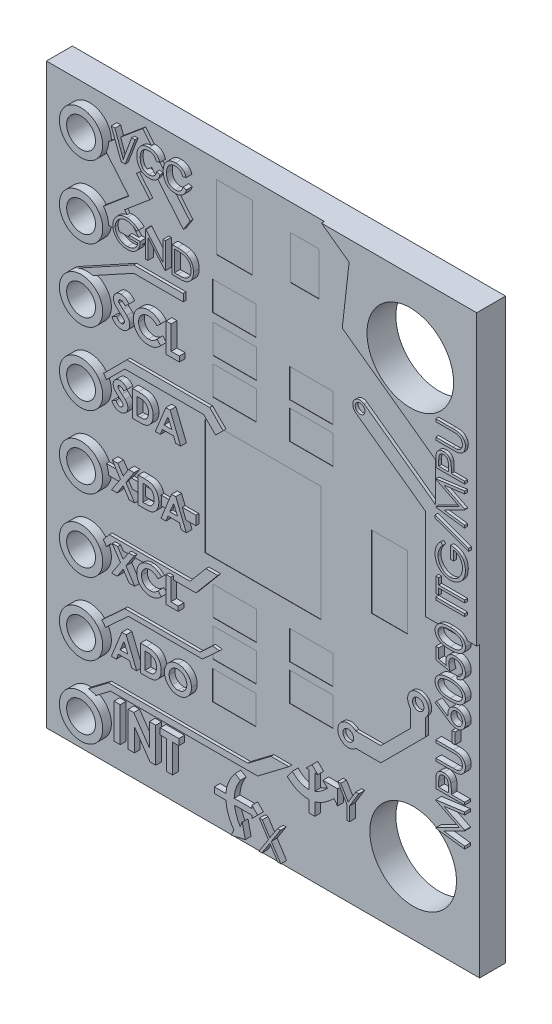
SolidWorks part; units mm, degrees
ref_plane "Plan de face" through (0, 0, 0) normal (0, 0, 1) x (1, 0, 0)
ref_plane "Plan de dessus" through (0, 0, 0) normal (0, 1, 0) x (1, 0, 0)
ref_plane "Plan de droite" through (0, 0, 0) normal (1, 0, 0) x (0, 0, -1)
sketch "Esquisse1" plane through (0, 0, 0) normal (0, 0, 1) x (1, 0, 0)
  line L0 (0, 0) -> (0, 9.701) construction
  line L1 (7.5, -10) -> (-7.5, -10)
  line L2 (7.5, -10) -> (7.5, 10)
  line L3 (7.5, 10) -> (-7.5, 10)
  line L4 (-7.5, -10) -> (-7.5, 10)
  line L5 (7.5, -10) -> (-7.5, 10) construction
  line L6 (7.5, 10) -> (-7.5, -10) construction
  line L7 (-7.2449, 0) -> (8.3434, 0) construction
  circle A0 centre (5.2, 7.5) radius 1.5
  circle A1 centre (5.2, -7.5) radius 1.5
  point P0 (0, 0)
  dimension "D3" = 3
  dimension "D1" = 20
  dimension "D2" = 15
  dimension "D4" = 2.5
  dimension "D5" = 2.3
extrude "Boss.-Extru.1" add sketch "Esquisse1" along normal blind 0.9
sketch "Esquisse2" plane through (0, 0, 0.9) normal (0, 0, 1) x (1, 0, 0)
  line L0 (-7.5, 10) -> (-7.5, -10) construction
  line L1 (7.5, 10) -> (-7.5, 10) construction
  circle A0 centre (-6, 8.75) radius 0.75
  circle A1 centre (-6, 8.75) radius 0.5
  dimension "D1" = 1.5
  dimension "D2" = 0.25
  dimension "D5" = 1
  dimension "D3" = 1.5
  dimension "D4" = 1.25
extrude "Enlèv. mat.-Extru.3" cut sketch "Esquisse2" against normal through all contours A1 region at (-6, 8.75, 0.9)
extrude "Boss.-Extru.2" add sketch "Esquisse2<3>" along normal blind 0.3 contours A1 | A0
sketch "Esquisse2<3>" plane through (0, 0, 0.9) normal (0, 0, 1) x (1, 0, 0) same geometry as "Esquisse2"
pattern_linear "Répétition linéaire1" count 8 spacing 2.5 along (0, -1, 0) of "Enlèv. mat.-Extru.3", "Boss.-Extru.2"
sketch "Esquisse4" plane through (0, 0, 0.9) normal (0, 0, 1) x (1, 0, 0)
  line L0 (-5.6839, -8.0698) -> (-5.1788, -7.6865)
  line L1 (-5.1788, -7.6865) -> (-0.0869, -7.6865)
  line L2 (-5.3559, -5.8657) -> (-4.5626, -5.1342)
  line L3 (-5.9485, -8.0018) -> (-5.25, -7.4716)
  line L4 (-5.25, -7.4716) -> (-0.425, -7.4716)
  line L5 (-0.425, -7.4716) -> (0.3769, -6.863)
  line L6 (-0.0869, -7.6865) -> (0.9981, -6.863)
  line L7 (-4.5626, -5.1342) -> (-1.9962, -5.1342)
  line L8 (-1.9962, -5.1342) -> (-1.4096, -4.5933)
  line L9 (-1.6459, -4.5662) -> (-2.0788, -4.9655)
  line L10 (-2.0788, -4.9655) -> (-4.6846, -4.9655)
  line L11 (-4.6846, -4.9655) -> (-5.4857, -5.7041)
  line L12 (-5.3211, -3.4313) -> (-5.1788, -3.2623)
  line L13 (-5.1788, -3.2623) -> (-2.2245, -3.2623)
  line L14 (-2.2245, -3.2623) -> (-1.4657, -2.3614)
  line L15 (-1.4657, -2.3614) -> (-1.876, -2.3614)
  line L16 (-1.876, -2.3614) -> (-2.4268, -3.0153)
  line L17 (-2.4268, -3.0153) -> (-5.2223, -3.0153)
  line L18 (-5.2223, -3.0153) -> (-5.4303, -3.2623)
  line L19 (-5.25, -1.25) -> (-2.2245, -1.25)
  line L20 (-5.3211, -0.9313) -> (-2.2245, -0.9313)
  line L21 (-5.326, 1.579) -> (-4.6846, 2.2204)
  line L22 (-4.6846, 2.2204) -> (-1.952, 2.2204)
  line L23 (-1.952, 2.2204) -> (-1.5418, 1.8102)
  line L24 (-1.5418, 1.8102) -> (-1.2801, 2.0719)
  line L25 (-1.2801, 2.0719) -> (-1.744, 2.5358)
  line L26 (-1.744, 2.5358) -> (-4.6086, 2.5358)
  line L27 (-4.6086, 2.5358) -> (-5.4195, 1.7249)
  line L28 (-2.2245, -0.9313) -> (-2.2245, -1.25)
  line L29 (0.3769, -6.863) -> (0.9981, -6.863)
  line L30 (-5.7904, 4.4701) -> (-4.3767, 5.2455)
  line L31 (-4.3767, 5.2455) -> (-2.6617, 5.2455)
  line L32 (-2.6617, 5.2455) -> (-2.6617, 5.4958)
  line L33 (-2.6617, 5.4958) -> (-4.3767, 5.4958)
  line L34 (-4.3767, 5.4958) -> (-6.3607, 4.4076)
  line L35 (-5.25, 6.25) -> (-4.0664, 6.25)
  line L36 (-4.0664, 6.25) -> (-4.6907, 6.9959)
  line L37 (-4.6907, 6.9959) -> (-3.8171, 7.7316)
  line L38 (-3.8171, 7.7316) -> (-4.2836, 8.289)
  line L39 (-4.2836, 8.289) -> (-3.7546, 8.7317)
  line L40 (-3.7546, 8.7317) -> (-2.6559, 7.4189)
  line L41 (-4.0664, 9.7406) -> (-5.25, 8.75)
  line L42 (-5.3315, 8.41) -> (-4.5476, 7.4734)
  line L43 (-4.5476, 7.4734) -> (-5.4264, 6.7332)
  line L44 (-4.0664, 9.7406) -> (-2.4268, 7.7815)
  line L45 (-1.6459, -4.5662) -> (-1.4096, -4.5933)
  line L46 (6.0756, 4.8784) -> (2.8432, 7.2132)
  line L47 (2.8432, 7.2132) -> (3.0831, 9.3079)
  line L48 (3.0831, 9.3079) -> (2.1248, 10)
  line L49 (7.5, 10) -> (-7.5, 10) construction
  line L50 (6.0756, 4.8784) -> (6.0756, 3.5316)
  line L51 (6.0756, 3.5316) -> (3.6093, 5.3131)
  line L52 (3.3136, 4.9036) -> (5.7336, 3.1556)
  line L53 (5.7336, 3.1556) -> (5.7336, 0)
  line L54 (5.7336, 0) -> (7.5, 0)
  line L55 (7.5, -10) -> (7.5, 10) construction
  line L56 (5.7336, -3.0153) -> (5.7336, -3.6039)
  line L57 (5.7336, -3.6039) -> (4.18, -5.1574)
  line L58 (4.18, -5.1574) -> (3.3136, -5.1574)
  line L59 (3.3136, -4.639) -> (4.18, -4.639)
  line L60 (4.18, -4.639) -> (5.2151, -3.6039)
  line L61 (5.2151, -3.6039) -> (5.2151, -3.0153)
  line L62 (-2.4268, 7.7815) -> (-2.6559, 7.4189)
  circle A0 centre (-6, -8.75) radius 0.75 construction
  circle A1 centre (-6, -8.75) radius 0.75 construction
  arc A2 (-5.6839, -8.0698) -> (-5.9485, -8.0018) centre (-6, -8.75) ccw
  circle A3 centre (-6, -6.25) radius 0.75 construction
  circle A4 centre (-6, -3.75) radius 0.75 construction
  circle A5 centre (-6, -3.75) radius 0.75 construction
  circle A6 centre (-6, -1.25) radius 0.75 construction
  circle A7 centre (-6, 1.25) radius 0.75 construction
  circle A8 centre (-6, 3.75) radius 0.75 construction
  circle A9 centre (-6, 3.75) radius 0.75 construction
  arc A10 (-5.7904, 4.4701) -> (-6.3607, 4.4076) centre (-6, 3.75) ccw
  circle A11 centre (-6, 6.25) radius 0.75 construction
  circle A12 centre (-6, 8.75) radius 0.75 construction
  circle A13 centre (-6, 8.75) radius 0.75 construction
  arc A14 (-5.3315, 8.41) -> (-5.25, 8.75) centre (-6, 8.75) ccw
  circle A16 centre (-6, 6.25) radius 0.75 construction
  arc A17 (-5.25, 6.25) -> (-5.4264, 6.7332) centre (-6, 6.25) ccw
  circle A18 centre (-6, 1.25) radius 0.75 construction
  arc A19 (-5.326, 1.579) -> (-5.4195, 1.7249) centre (-6, 1.25) ccw
  circle A20 centre (-6, -1.25) radius 0.75 construction
  arc A21 (-5.25, -1.25) -> (-5.3211, -0.9313) centre (-6, -1.25) ccw
  circle A22 centre (-6, -6.25) radius 0.75 construction
  arc A23 (-5.3559, -5.8657) -> (-5.4857, -5.7041) centre (-6, -6.25) ccw
  arc A24 (-5.3211, -3.4313) -> (-5.4303, -3.2623) centre (-6, -3.75) ccw
  arc A25 (3.3136, 4.9036) -> (3.6093, 5.3131) centre (3.4615, 5.1083) cw
  arc A26 (3.6093, 5.3131) -> (3.3136, 4.9036) centre (3.4615, 5.1083) ccw
  circle A27 centre (3.4615, 5.1083) radius 0.1681
  arc A28 (5.2151, -3.0153) -> (5.7336, -3.0153) centre (5.4743, -2.7561) cw
  arc A29 (3.3136, -4.639) -> (3.3136, -5.1574) centre (3.0544, -4.8982) ccw
  circle A30 centre (3.0544, -4.8982) radius 0.1869
  circle A31 centre (5.4743, -2.7561) radius 0.1967
  circle M44 centre (-6, 8.75) radius 0.75
  circle M45 centre (5.2, 7.5) radius 1.5
  line M48 (7.5, -10) -> (7.5, 10)
  line M49 (7.5, 10) -> (-7.5, 10)
  circle M51 centre (-6, 6.25) radius 0.75
extrude "Boss.-Extru.3" add sketch "Esquisse4" along normal blind 0.1 contours A25 L52 L53 L54 L48 L47 L46 L50 L51 A27 M48 M49 M45 | L59 A29 L58 L57 L56 A28 L61 L60 A31 A30 | L62 L44 L41 L42 L43 L35 L36 L37 L38 L39 L40 M44 M51 | L5 L29 L6 L1 L0 A2 L3 L4 | L24 L25 L26 L27 A19 L21 L22 L23 | L33 L34 A10 L30 L31 L32 | L20 L28 L19 A21 | L14 L15 L16 L17 L18 A24 L12 L13 | L8 L45 L9 L10 L11 A23 L2 L7 region at (-4.2587, 8.0814, 0.9) region at (5.8792, 5.6723, 0.9) region at (5.6909, -3.3096, 0.9)
sketch "Esquisse12" plane through (0, 0, 0.9) normal (0, 0, 1) x (1, 0, 0)
  line L0 (-5.0695, 8.4732) -> (-2.0314, 8.4732) construction
  line L1 (-5.0695, 5.9732) -> (-2.0314, 5.9732) construction
  line L2 (-5.0695, 3.4732) -> (-2.0314, 3.4732) construction
  line L3 (-5.0695, 0.9732) -> (-2.0314, 0.9732) construction
  line L4 (-5.0695, -1.5268) -> (-2.0314, -1.5268) construction
  line L5 (-5.0695, -4.0268) -> (-2.0314, -4.0268) construction
  line L6 (-5.0695, -6.5268) -> (-2.0314, -6.5268) construction
  line L7 (-5.0695, -9.0268) -> (-2.0314, -9.0268) construction
  text T0 "VCC" font "@Arial Unicode MS" height 0.9
  text T1 "GND" font "Century Gothic" height 0.9
  text T2 "SCL\r\n" font "Century Gothic" height 1
  text T3 "SDA" font "Century Gothic" height 0.9
  text T4 "XDA" font "Century Gothic" height 0.9
  text T5 "XCL" font "Century Gothic" height 0.9
  text T6 "ADO" font "Century Gothic" height 0.9
  text T7 "INT" font "Century Gothic" height 1.2
  dimension "D1" = 8
extrude "Boss.-Extru.4" add sketch "Esquisse12" along normal blind 0.2
sketch "Esquisse13" plane through (0, 0, 0.9) normal (0, 0, 1) x (1, 0, 0)
  line L0 (-1.4855, -8.8592) -> (-1.085, -8.8592)
  line L1 (-0.1855, -8.8592) -> (-0.1855, -8.9592)
  line L2 (-0.1855, -8.9592) -> (0.0145, -8.7592)
  line L3 (0.0145, -8.7592) -> (-0.1855, -8.5592)
  line L4 (-0.1855, -8.5592) -> (-0.1855, -8.6592)
  line L5 (-0.1855, -8.6592) -> (-0.7975, -8.6592)
  line L6 (-1.4855, -8.6592) -> (-1.4855, -8.8592)
  line L7 (1.997, -7.8033) -> (1.997, -7.3665)
  line L8 (1.997, -6.5033) -> (2.097, -6.5033)
  line L9 (2.097, -6.5033) -> (1.897, -6.3033)
  line L10 (1.897, -6.3033) -> (1.697, -6.5033)
  line L11 (1.697, -6.5033) -> (1.797, -6.5033)
  line L12 (1.797, -6.5033) -> (1.797, -7.0998)
  line L13 (1.797, -7.8033) -> (1.997, -7.8033)
  line L14 (-0.8058, -9.6098) -> (-0.9072, -9.8186)
  line L15 (-0.9072, -9.8186) -> (-0.4139, -9.7084)
  line L16 (-0.4139, -9.7084) -> (-0.5192, -9.2372)
  line L17 (-0.5192, -9.2372) -> (-0.5935, -9.4085)
  line L18 (-0.5829, -8.0126) -> (-0.771, -7.9044)
  line L19 (2.4338, -6.7421) -> (2.2729, -6.5837)
  line L20 (2.2729, -6.5837) -> (2.783, -6.5837)
  line L21 (2.783, -6.5837) -> (2.783, -7.1)
  line L22 (2.783, -7.1) -> (2.6565, -6.9399)
  line L23 (1.2146, -6.8436) -> (1.0366, -7.0862)
  line L24 (-1.0844, -8.6592) -> (-1.4855, -8.6592)
  line L25 (1.797, -7.3995) -> (1.797, -7.8033)
  line L26 (-0.7867, -8.8592) -> (-0.1855, -8.8592)
  line L27 (1.997, -7.0528) -> (1.997, -6.5033)
  line L28 (0.0145, -9.8186) -> (1.6804, -9.8186) construction
  line L29 (2.7344, -7.3665) -> (3.9669, -7.3665) construction
  spline S0 degree 2 poles (-0.771, -7.9044) (-1.0541, -8.255) (-1.0844, -8.6592) knots 0 0 0 0.442891 0.442891 0.442891
  spline S1 degree 3 poles (-0.5829, -8.0126) (-0.7189, -8.2209) (-0.7905, -8.4364) (-0.7975, -8.6592) knots 0 0 0 0 0.480183 0.480183 0.480183 0.480183
  spline S2 degree 3 poles (1.0366, -7.0862) (1.2858, -7.3076) (1.5393, -7.412) (1.797, -7.3995) knots 0 0 0 0 0.477983 0.477983 0.477983 0.477983
  spline S3 degree 3 poles (1.2146, -6.8436) (1.4015, -7.0294) (1.5957, -7.1148) (1.797, -7.0998) knots 0 0 0 0 0.495666 0.495666 0.495666 0.495666
  spline S4 degree 3 poles (-1.085, -8.8592) (-1.0812, -8.9137) (-1.0473, -9.18) (-0.9384, -9.4353) (-0.8096, -9.608) (-0.8058, -9.6098) knots 0.552421 0.552421 0.552421 0.552421 0.642107 0.993388 1 1 1 1
  spline S5 degree 2 poles (-0.7867, -8.8592) (-0.7499, -9.1271) (-0.5935, -9.4085) knots 0.622472 0.622472 0.622472 1 1 1
  spline S6 degree 3 poles (1.997, -7.0528) (2.1392, -6.9971) (2.2848, -6.8935) (2.4338, -6.7421) knots 0.657917 0.657917 0.657917 0.657917 1 1 1 1
  spline S7 degree 2 poles (1.997, -7.3665) (2.3223, -7.2754) (2.6565, -6.9399) knots 0.601114 0.601114 0.601114 1 1 1
  text T0 "Y" font "Century Gothic" height 1
  text T1 "X" font "Century Gothic" height 1
  dimension "D1" = 0.2
  dimension "D2" = 1.3
  dimension "D3" = 0.1
  dimension "D4" = 0.1
  dimension "D5" = 0.2
  dimension "D6" = 0.2
  dimension "D7" = 1.3
  dimension "D8" = 0.1
  dimension "D9" = 0.2
  dimension "D10" = 0.1
extrude "Boss.-Extru.5" add sketch "Esquisse13" along normal blind 0.2
sketch "Esquisse14" plane through (0, 0, 0.9) normal (0, 0, 1) x (1, 0, 0)
  line L0 (7.1827, -6.2733) -> (7.1827, 6.2188) construction
  text T0 "MPU-6050 ITG/MPU" font "Century Gothic" height 1
extrude "Boss.-Extru.6" add sketch "Esquisse14" along normal blind 0.2
sketch "Esquisse15" plane through (0, 0, 0.9) normal (0, 0, 1) x (1, 0, 0)
  line L0 (-1.7334, 4.0536) -> (-0.2334, 4.0536)
  line L1 (2, -2) -> (-2, -2)
  line L2 (2, -2) -> (2, 2)
  line L3 (2, 2) -> (-2, 2)
  line L4 (-2, -2) -> (-2, 2)
  line L5 (2, -2) -> (-2, 2) construction
  line L6 (2, 2) -> (-2, -2) construction
  line L7 (-0.3655, 7.1404) -> (-1.6155, 7.1404)
  line L8 (-0.3655, 7.1404) -> (-0.3655, 9.3904)
  line L9 (-0.3655, 9.3904) -> (-1.6155, 9.3904)
  line L10 (-1.6155, 7.1404) -> (-1.6155, 9.3904)
  line L11 (-0.3655, 7.1404) -> (-1.6155, 9.3904) construction
  line L12 (-0.3655, 9.3904) -> (-1.6155, 7.1404) construction
  line L13 (5.0118, -0.9331) -> (3.7618, -0.9331)
  line L14 (5.0118, -0.9331) -> (5.0118, 1.5669)
  line L15 (5.0118, 1.5669) -> (3.7618, 1.5669)
  line L16 (3.7618, -0.9331) -> (3.7618, 1.5669)
  line L17 (5.0118, -0.9331) -> (3.7618, 1.5669) construction
  line L18 (5.0118, 1.5669) -> (3.7618, -0.9331) construction
  line L19 (1.9439, 7.5822) -> (0.9439, 7.5822)
  line L20 (1.9439, 7.5822) -> (1.9439, 9.0822)
  line L21 (1.9439, 9.0822) -> (0.9439, 9.0822)
  line L22 (0.9439, 7.5822) -> (0.9439, 9.0822)
  line L23 (1.9439, 7.5822) -> (0.9439, 9.0822) construction
  line L24 (1.9439, 9.0822) -> (0.9439, 7.5822) construction
  line L25 (-1.7405, 6.338) -> (-0.2405, 6.338)
  line L26 (-1.7405, 6.338) -> (-1.7405, 5.338)
  line L27 (-1.7405, 5.338) -> (-0.2405, 5.338)
  line L28 (-0.2405, 6.338) -> (-0.2405, 5.338)
  line L29 (-1.7405, 6.338) -> (-0.2405, 5.338) construction
  line L30 (-1.7405, 5.338) -> (-0.2405, 6.338) construction
  line L31 (0.9166, 5.0536) -> (2.4166, 5.0536)
  line L32 (0.9166, 5.0536) -> (0.9166, 4.0536)
  line L33 (0.9166, 4.0536) -> (2.4166, 4.0536)
  line L34 (2.4166, 5.0536) -> (2.4166, 4.0536)
  line L35 (0.9166, 5.0536) -> (2.4166, 4.0536) construction
  line L36 (0.9166, 4.0536) -> (2.4166, 5.0536) construction
  line L37 (-1.7334, 5.0536) -> (-1.7334, 4.0536)
  line L38 (0.9166, 2.8036) -> (2.4166, 2.8036)
  line L39 (-1.7334, 5.0536) -> (-0.2334, 5.0536)
  line L40 (-0.2334, 5.0536) -> (-0.2334, 4.0536)
  line L41 (-1.7334, 2.8036) -> (-0.2334, 2.8036)
  line L42 (-1.7334, 3.8036) -> (-1.7334, 2.8036)
  line L43 (0.9166, 3.8036) -> (2.4166, 3.8036) [skipped]
  line L44 (0.9166, 3.8036) -> (0.9166, 2.8036) [skipped]
  line L45 (2.4166, 3.8036) -> (2.4166, 2.8036) [skipped]
  line L46 (-1.7334, 3.8036) -> (-0.2334, 3.8036)
  line L47 (-0.2334, 3.8036) -> (-0.2334, 2.8036)
  line L49 (0.9166, 3.8036) -> (0.9166, 2.8036)
  line L50 (0.9166, 3.8036) -> (2.4166, 3.8036)
  line L51 (2.4166, 3.8036) -> (2.4166, 2.8036)
  line L52 (0, 0) -> (-3.2166, 0) construction
  line L53 (0.9166, -4.0536) -> (2.4166, -5.0536) construction
  line L54 (0.9166, -5.0536) -> (2.4166, -4.0536) construction
  line L55 (2.4166, -3.8036) -> (2.4166, -2.8036)
  line L56 (0.9166, -3.8036) -> (2.4166, -3.8036)
  line L57 (0.9166, -3.8036) -> (0.9166, -2.8036)
  line L58 (0.9166, -2.8036) -> (2.4166, -2.8036)
  line L59 (-0.2334, -3.8036) -> (-0.2334, -2.8036)
  line L60 (-1.7334, -3.8036) -> (-0.2334, -3.8036)
  line L61 (-1.7334, -3.8036) -> (-1.7334, -2.8036)
  line L62 (-1.7334, -2.8036) -> (-0.2334, -2.8036)
  line L63 (-0.2334, -5.0536) -> (-0.2334, -4.0536)
  line L64 (-1.7334, -5.0536) -> (-0.2334, -5.0536)
  line L66 (-1.7334, -5.0536) -> (-1.7334, -4.0536)
  line L67 (2.4166, -5.0536) -> (2.4166, -4.0536)
  line L68 (0.9166, -4.0536) -> (2.4166, -4.0536)
  line L69 (0.9166, -5.0536) -> (0.9166, -4.0536)
  line L70 (0.9166, -5.0536) -> (2.4166, -5.0536)
  line L71 (-1.7334, -4.0536) -> (-0.2334, -4.0536)
  line L72 (-1.7405, -5.338) -> (-0.2405, -6.338) construction
  line L73 (-1.7405, -6.338) -> (-0.2405, -5.338) construction
  line L74 (-0.2405, -6.338) -> (-0.2405, -5.338)
  line L75 (-1.7405, -5.338) -> (-0.2405, -5.338)
  line L76 (-1.7405, -6.338) -> (-1.7405, -5.338)
  line L77 (-1.7405, -6.338) -> (-0.2405, -6.338)
  line L78 (0.9166, 2.8036) -> (2.4166, 2.8036) [skipped]
  point P0 (0, 0)
  point P5 (-0.9905, 8.2654)
  point P11 (4.3868, 0.3169)
  point P16 (1.4439, 8.3322)
  point P21 (-0.9905, 5.838)
  point P26 (1.6666, 4.5536)
  point P31 (1.5309, 3.5286)
  point P70 (1.5309, -3.5286)
  point P71 (1.6666, -4.5536)
  point P76 (-0.9905, -5.838)
  dimension "D1" = 4
  dimension "D2" = 4
  dimension "D3" = 2.25
  dimension "D4" = 1.25
  dimension "D5" = 2.5
  dimension "D6" = 1.25
  dimension "D7" = 1.5
  dimension "D8" = 1
  dimension "D9" = 1.5
  dimension "D10" = 1
  dimension "D11" = 1.5
  dimension "D12" = 1
  dimension "D13" = 2
  dimension "D14" = 2
  dimension "D15" = 2
extrude "Enlèv. mat.-Extru.4" cut sketch "Esquisse15" against normal blind 0.01
